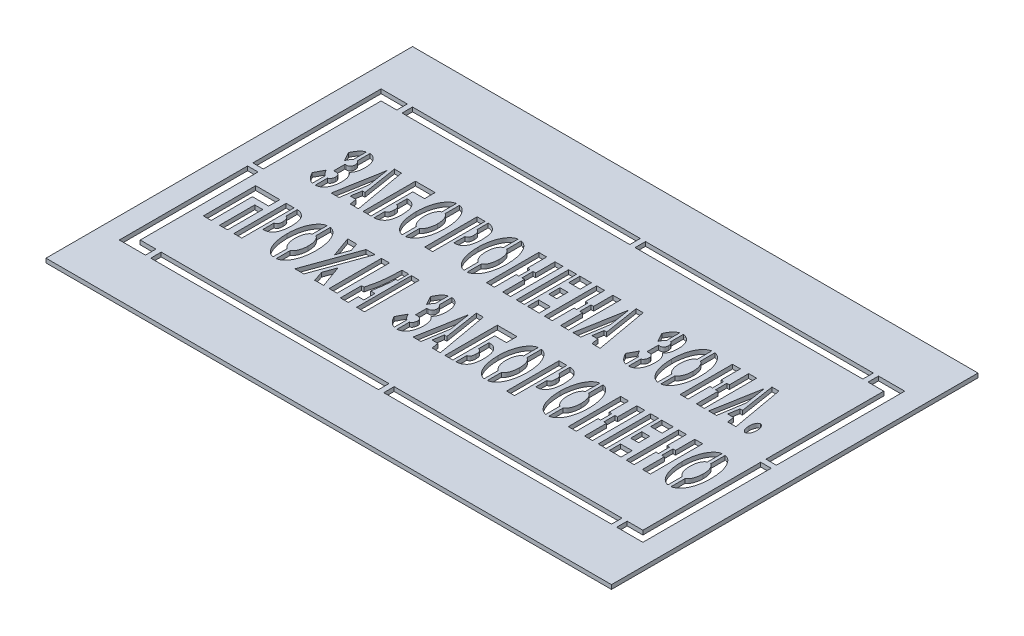
SolidWorks part; units mm, degrees
ref_plane "Спереди" through (0, 0, 0) normal (0, 0, 1) x (1, 0, 0)
ref_plane "Сверху" through (0, 0, 0) normal (0, 1, 0) x (1, 0, 0)
ref_plane "Справа" through (0, 0, 0) normal (1, 0, 0) x (0, 0, -1)
sketch "Эскиз1" plane through (0, 0, 0) normal (0, 1, 0) x (1, 0, 0)
  line L0 (25, 250) -> (25, 240)
  line L1 (0, 250) -> (500, 250)
  line L2 (0, 250) -> (0, 0)
  line L3 (0, 0) -> (500, 0)
  line L4 (500, 250) -> (500, 0)
  line L5 (30, 250) -> (30, 240)
  line L6 (0, 125) -> (-49.6951, 125) construction
  line L7 (10, 240) -> (490, 240)
  line L8 (10, 240) -> (10, 10)
  line L9 (10, 10) -> (490, 10)
  line L10 (490, 240) -> (490, 10)
  line L11 (250, 250) -> (250, 284.0129) construction
  line L12 (470, 250) -> (470, 240)
  line L13 (475, 250) -> (475, 240)
  line L14 (247.5, 250) -> (247.5, 240)
  line L15 (252.5, 250) -> (252.5, 240)
  line L16 (475, 0) -> (475, 10)
  line L17 (470, 0) -> (470, 10)
  line L18 (30, 0) -> (30, 10)
  line L19 (25, 0) -> (25, 10)
  line L20 (252.5, 0) -> (252.5, 10)
  line L21 (247.5, 0) -> (247.5, 10)
  line L22 (0, 127.5) -> (10, 127.5)
  line L23 (0, 122.5) -> (10, 122.5)
  line L24 (500, 122.5) -> (490, 122.5)
  line L25 (500, 127.5) -> (490, 127.5)
  line L27 (-20, -50) -> (520, -50)
  line L28 (-20, -50) -> (-20, 300)
  line L29 (-20, 300) -> (520, 300)
  line L30 (520, -50) -> (520, 300)
  point P0 (0, 0)
  point P6 (0, 0)
  dimension "D1" = 500
  dimension "D2" = 250
  dimension "D3" = 10
  dimension "D4" = 10
  dimension "D5" = 10
  dimension "D6" = 10
  dimension "D7" = 5
  dimension "D8" = 15
  dimension "D9" = 5
  dimension "D10" = 5
  dimension "D11" = 540
  dimension "D12" = 350
  dimension "D13" = 20
  dimension "D14" = 50
extrude "Бобышка-Вытянуть1" add sketch "Эскиз1" along normal blind 4 contours L10 L7 L8 L9 | L19 L3 L18 L9 | L21 L3 L20 L9 | L17 L3 L16 L9 | L4 L25 L10 L24 | L13 L1 L12 L7 | L15 L1 L14 L7 | L0 L7 L5 L1 | L2 L23 L8 L22 | L27 L30 L29 L28 L1 L4 L3 L2 region at (27.5, 0, -245) region at (250, 0, -125) region at (5, 0, -125) region at (250, 0, -245) region at (472.5, 0, -245) region at (27.5, 0, -5) region at (250, 0, -5) region at (495, 0, -125) region at (472.5, 0, -5) region at (-13.5649, 0, -125)
sketch "Эскиз2" plane through (0, 4, 0) normal (0, 1, 0) x (1, 0, 0)
  line L0 (14.7357, 140) -> (485.2643, 140) construction
  line L2 (250, 140) -> (250, 300) construction
  line L3 (-20, 300) -> (520, 300) construction
  line L4 (14.7357, 60) -> (485.2643, 60) construction
  line L5 (485.2643, 60) -> (485.2643, 140) construction
  line L6 (14.7357, 140) -> (14.7357, 60) construction
  line L7 (-20, 125) -> (-122.4254, 125) construction
  line L8 (-20, -50) -> (-20, 300) construction
  line L12 (0, 0) -> (25, 0) construction
  text T0 "ЗАБОРОНЕНА ЗОНА." font "Sargento Gorila" height 50
  text T1 "ПРОХIД ЗАБОРОНЕНО" font "Sargento Gorila" height 50
  dimension "D1" = 15
  dimension "D2" = 65
  dimension "D3" = 60
extrude "Вырез-Вытянуть1" cut sketch "Эскиз2" against normal blind 4
